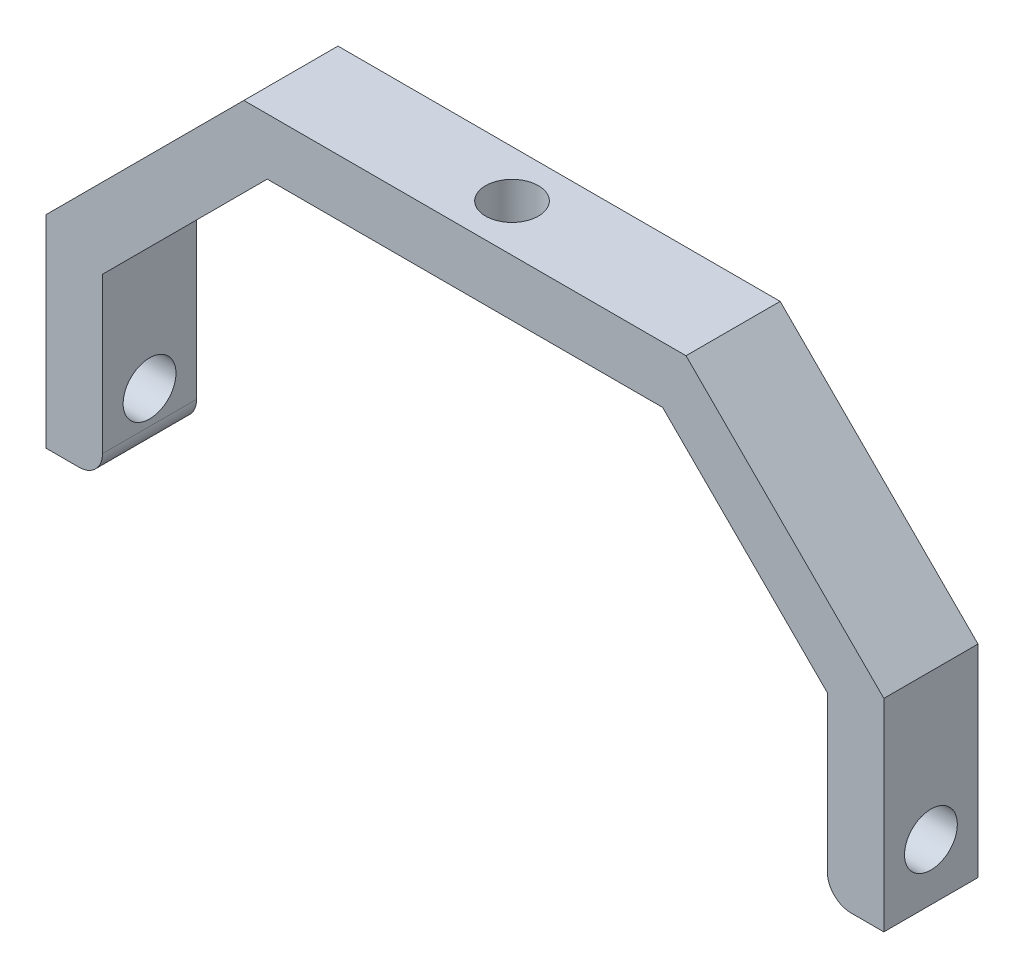
SolidWorks part; units mm, degrees
material "ABS"
ref_plane "Front Plane" through (0, 0, 0) normal (0, 0, 1) x (1, 0, 0)
ref_plane "Top Plane" through (0, 0, 0) normal (0, 1, 0) x (1, 0, 0)
ref_plane "Right Plane" through (0, 0, 0) normal (1, 0, 0) x (0, 0, -1)
sketch "Sketch1" plane through (0, 0, 0) normal (0, 0, 1) x (1, 0, 0)
  line L0 (-44.5, -6) -> (-38.5, -6)
  line L1 (-38.5, -6) -> (-38.5, 13)
  line L2 (-38.5, 13) -> (-21, 30.5)
  line L3 (-21, 30.5) -> (21, 30.5)
  line L4 (21, 30.5) -> (38.5, 13)
  line L5 (38.5, 13) -> (38.5, -6)
  line L6 (38.5, -6) -> (44.5, -6)
  line L7 (44.5, -6) -> (44.5, 15.4853)
  line L8 (44.5, 15.4853) -> (23.4853, 36.5)
  line L9 (23.4853, 36.5) -> (-23.4853, 36.5)
  line L10 (-23.4853, 36.5) -> (-44.5, 15.4853)
  line L11 (-44.5, 15.4853) -> (-44.5, -6)
  point P13 (0, 30.5)
  dimension "D1" = 77
  dimension "D2" = 6
  dimension "D3" = 6
  dimension "D4" = 6
  dimension "D5" = 6
  dimension "D6" = 6
  dimension "D7" = 45
  dimension "D8" = 42.5
  dimension "D9" = 6
  dimension "D10" = 17.5
extrude "Boss-Extrude1" add sketch "Sketch1" along normal blind 10
sketch "Sketch3" plane through (0, 0, 0) normal (1, 0, 0) x (0, 0, -1)
  line L0 (-10, -6) -> (0, -6) construction
  circle A0 centre (-5, 0) radius 2.8067
  point P5 (-5, -6)
  dimension ".221" = 5.6134
  dimension "D1" = 6
extrude "Cut-Extrude1" cut sketch "Sketch3" along normal through all
ref_axis "Axis1" through (0, 0, 0) along (0, 0, 1)
fillet "Fillet1" radius 2.5 2 edges at (38.5, -6, 5) (-38.5, -6, 5)
pattern_circular "CirPattern3" count 3 every 90 about axis through (0, 0, 0) along (0, 0, 1) of "Cut-Extrude1"
